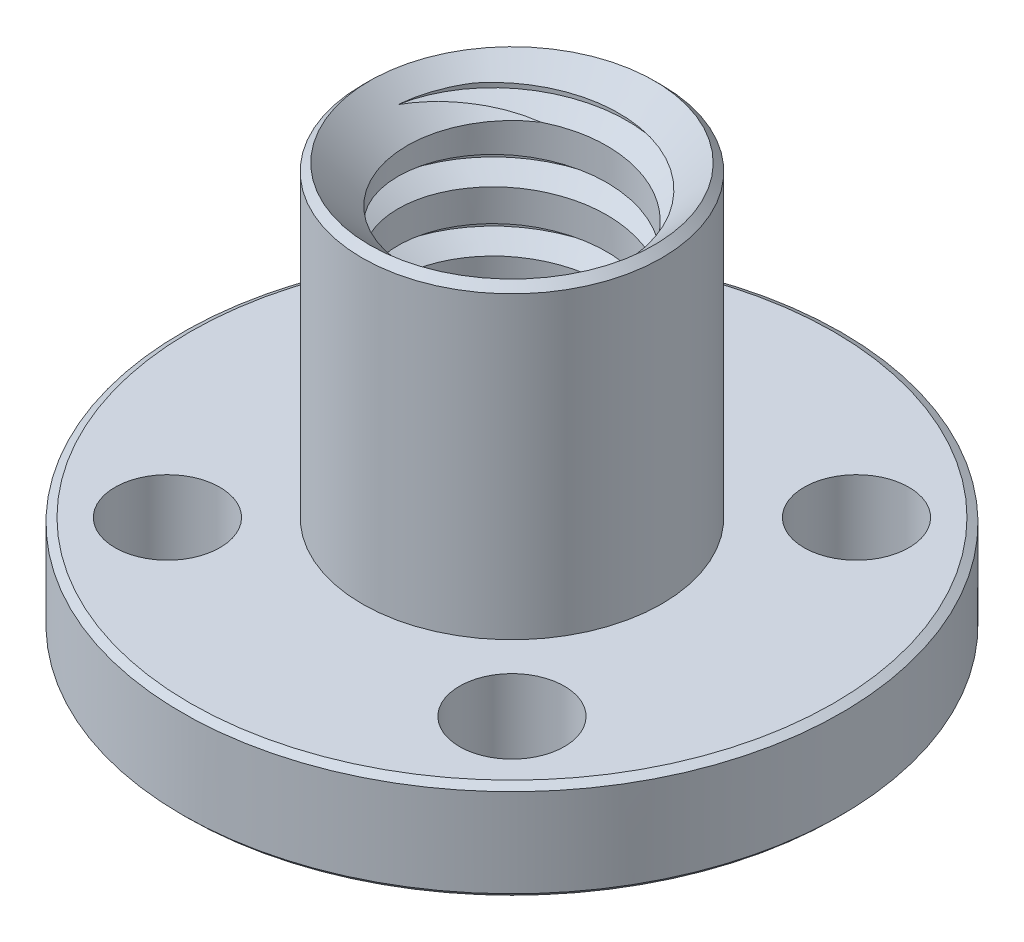
SolidWorks part; units mm, degrees
ref_plane "Front Plane" through (0, 0, 0) normal (0, 0, 1) x (1, 0, 0)
ref_plane "Top Plane" through (0, 0, 0) normal (0, 1, 0) x (1, 0, 0)
ref_plane "Right Plane" through (0, 0, 0) normal (1, 0, 0) x (0, 0, -1)
sketch "Sketch1" plane through (0, 0, 0) normal (0, 1, 0) x (1, 0, 0)
  circle A0 centre (0, 0) radius 11
  dimension "D1" = 22
extrude "Boss-Extrude1" add sketch "Sketch1" along normal blind 3.25
sketch "Sketch2" plane through (0, 0, 0) normal (0, -1, 0) x (1, 0, 0)
  circle A0 centre (0, 0) radius 5
  dimension "D1" = 10
extrude "Boss-Extrude2" add sketch "Sketch2" along normal blind 1.5
sketch "Sketch3" plane through (0, 3.25, 0) normal (0, 1, 0) x (1, 0, 0)
  circle A0 centre (0, 0) radius 5
  dimension "D1" = 10
extrude "Boss-Extrude3" add sketch "Sketch3" along normal blind 10.25
ref_axis "Axis1" through (0, 13.5, 0) along (0, -1, 0)
sketch "Sketch4" plane through (0, 3.25, 0) normal (0, 1, 0) x (1, 0, 0)
  line L1 (5.75, 5.75) -> (-5.75, 5.75) construction
  line L2 (5.75, 5.75) -> (5.75, -5.75) construction
  line L3 (5.75, -5.75) -> (-5.75, -5.75) construction
  line L4 (-5.75, 5.75) -> (-5.75, -5.75) construction
  line L5 (5.75, 5.75) -> (-5.75, -5.75) construction
  line L6 (5.75, -5.75) -> (-5.75, 5.75) construction
  circle A0 centre (-5.75, -5.75) radius 1.75
  circle A1 centre (-5.75, 5.75) radius 1.75
  circle A2 centre (5.75, 5.75) radius 1.75
  circle A3 centre (5.75, -5.75) radius 1.75
  point P0 (0, 0)
  point P16 (0, 0)
  dimension "D3" = 3.5
  dimension "D1" = 11.5
  dimension "D2" = 11.5
  dimension "D4" = 4
extrude "Cut-Extrude1" cut sketch "Sketch4" against normal up to surface (3.25 mm away) up to face at (0, 0, -5)
sketch "Sketch5" plane through (0, 13.5, 0) normal (0, 1, 0) x (1, 0, 0)
  circle A0 centre (0, 0) radius 3.5
  dimension "D1" = 7
extrude "Cut-Extrude2" cut sketch "Sketch5" against normal up to surface (15 mm away) up to face at (0, -1.5, -5)
chamfer "Chamfer1" distance 0.25 angle 45 1 edges at (0, 13.5, 5)
chamfer "Chamfer2" distance 0.15 angle 60 1 edges at (0, 3.25, 11) first distance on face at (0, 3.25, 11)
chamfer "Chamfer3" distance 0.15 angle 45 1 edges at (0, 0, 11)
thread "Thread1" pitch 1.25 method cut profile "Thread Profile2" start angle 0, offset 2, length 17.5, pitch 2, diameter 7
ref_plane "Plane2" through (-3.5, 15.5, 0) normal (0, 0, 1) x (-1, 0, 0)
sketch "Thread Profile2" plane through (-3.5, 15.5, 0) normal (0, 0, 1) x (-1, 0, 0)
  line L0 (0, 0) -> (0, 1.25) construction
  line L1 (0, 0) -> (0.6766, 0.3906)
  line L2 (0.6766, 0.3906) -> (0.6766, 0.5469)
  line L3 (0.6766, 0.5469) -> (0, 0.9375)
  line L4 (0.6766, 0.4687) -> (0, 0.4687) construction
  line L11 (0, 0) -> (0, 0.9375)
  point P2 (0, 0)
  dimension "Pitch" = 1.25
  dimension "Profile_Angle" = 60
  dimension "Profile_Land" = 0.1562
  dimension "Profile_Height" = 0.6766
ref_axis "Axis2" through (0, -1.5531, 0) along (0, 1, 0)
sketch "Sketch26" plane through (0, 13.5, 0) normal (0, 1, 0) x (1, 0, 0)
  circle A1 centre (0, 0) radius 4.75
  circle A2 centre (0, 0) radius 4.75
  dimension "D1" = 0
extrude "Cut-Extrude3" cut sketch "Sketch26" against normal blind 10 draft 45
sketch "Sketch27" plane through (0, -1.5, 0) normal (0, -1, 0) x (1, 0, 0)
  circle A0 centre (0, 0) radius 4.5
  dimension "D1" = 9
extrude "Cut-Extrude4" cut sketch "Sketch27" against normal blind 10 draft 45
